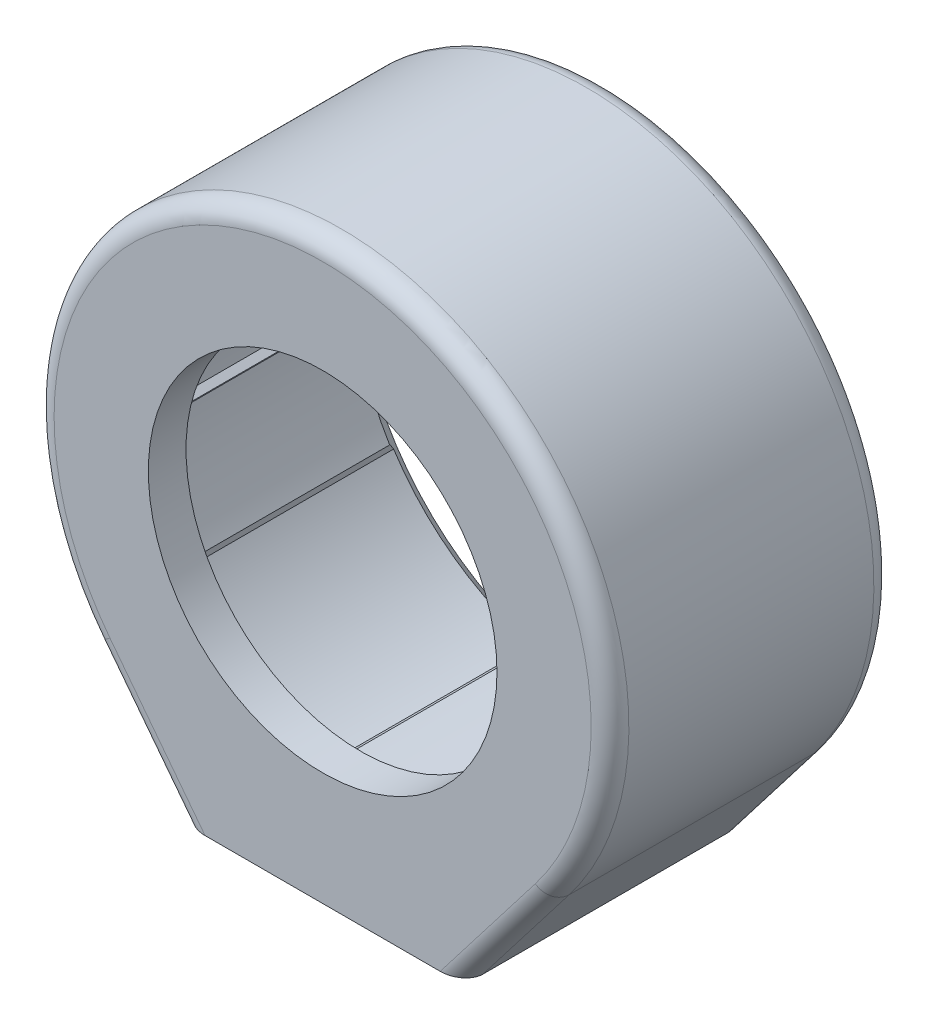
SolidWorks part; units mm, degrees
ref_plane "Ebene vorne" through (0, 0, 0) normal (0, 0, 1) x (1, 0, 0)
ref_plane "Ebene oben" through (0, 0, 0) normal (0, 1, 0) x (1, 0, 0)
ref_plane "Ebene rechts" through (0, 0, 0) normal (1, 0, 0) x (0, 0, -1)
sketch "Skizze1" plane through (0, 0, 0) normal (0, 0, 1) x (1, 0, 0)
  circle A0 centre (0, 0) radius 12.25
  circle A1 centre (0, 0) radius 15.25
  dimension "D1" = 24.5
  dimension "D2" = 3
extrude "Aufsatz-Linear austragen1" add sketch "Skizze1" along normal blind 15
sketch "Skizze2" plane through (0, 0, 15) normal (0, 0, 1) x (1, 0, 0)
  circle A0 centre (0, 0) radius 12.25 construction
  circle A1 centre (0, 0) radius 12.25
  circle A2 centre (0, 0) radius 9.25
  dimension "D1" = 3
extrude "Aufsatz-Linear austragen2" add sketch "Skizze2" against normal blind 2
sketch "Skizze3" plane through (0, 0, 15) normal (0, 0, 1) x (1, 0, 0)
  line L0 (0, 0) -> (0, -15.25) construction
  line L1 (7.5, -15.25) -> (-7.5, -15.25)
  line L2 (-7.5, -15.25) -> (-12.0786, -9.3097)
  line L3 (7.5, -15.25) -> (12.0786, -9.3097)
  circle A0 centre (0, 0) radius 15.25 construction
  arc A1 (-12.0786, -9.3097) -> (12.0786, -9.3097) centre (0, 0) ccw
  circle M4 centre (0, 0) radius 15.25
  dimension "D1" = 15
extrude "Aufsatz-Linear austragen3" add sketch "Skizze3" against normal through all contours L2 L1 M4 | L1 L3 M4 region at (6.8941, -14.018, 15) region at (-6.8941, -14.018, 15)
fillet "Verrundung1" radius 1 6 edges at (9.7893, -12.2799, 0) (-9.7893, -12.2799, 0) (9.7893, -12.2799, 15) (-9.7893, -12.2799, 15) (0, 15.25, 0) (0, 15.25, 15)
chamfer "Fase1" distance 1 angle 45 1 edges at (12.25, 0, 0)
sketch "Skizze4" plane through (0, 0, 0) normal (0, 0, -1) x (-1, 0, 0)
  line L0 (0, 0) -> (-4.8218, 11.6409)
  line L1 (0, 0) -> (0, 15.25) construction
  line L2 (0, 0) -> (4.8218, 11.6409)
  arc A0 (4.8218, 11.6409) -> (-4.8218, 11.6409) centre (0, 0) ccw
  arc A1 (12.0786, -9.3097) -> (-12.0786, -9.3097) centre (0, 0) ccw construction
  dimension "D1" = 25.2
  dimension "D2" = 45
extrude "Schnitt-Linear austragen1" cut sketch "Skizze4" against normal up to surface (13 mm away) up to face at (9.25, 0, 13)
pattern_circular "Kreismuster1" count 5 over 360 about axis through (0, 0, 15) along (0, 0, -1) of "Schnitt-Linear austragen1"
chamfer "Fase2" distance 0.3 angle 45 10 edges at (-2.9414, -12.2519, 6.825) (2.9414, -12.2519, 6.825) (10.7433, -6.5835, 6.825) (12.5612, -0.9886, 6.825) (9.5811, 8.183, 6.825) (4.8218, 11.6409, 6.825) (-4.8218, 11.6409, 6.825) (-9.5811, 8.183, 6.825) (-12.5612, -0.9886, 6.825) (-10.7433, -6.5835, 6.825)
